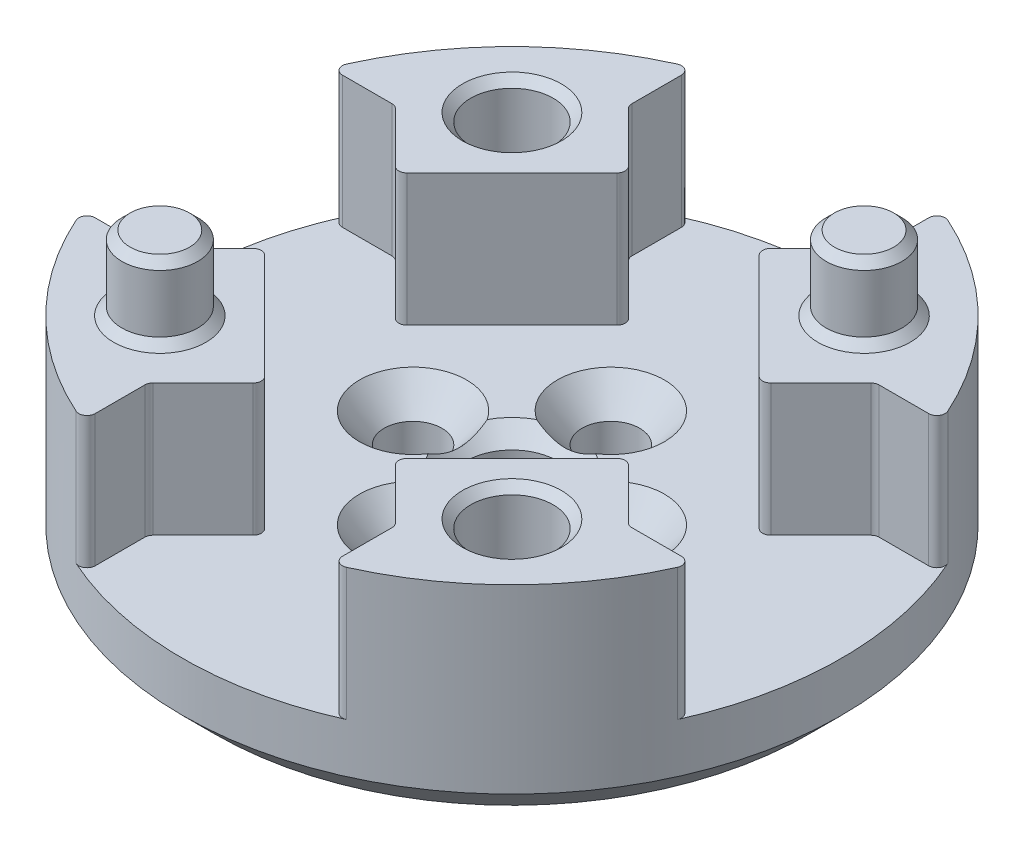
SolidWorks part; units mm, degrees
ref_plane "前视基准面" through (0, 0, 0) normal (0, 0, 1) x (1, 0, 0)
ref_plane "上视基准面" through (0, 0, 0) normal (0, 1, 0) x (1, 0, 0)
ref_plane "右视基准面" through (0, 0, 0) normal (1, 0, 0) x (0, 0, -1)
sketch "草图1" plane through (0, 0, 0) normal (0, 1, 0) x (1, 0, 0)
  circle A0 centre (0, 0) radius 20
  dimension "D1" = 40
extrude "凸台-拉伸1" add sketch "草图1" along normal blind 5
sketch "草图2" plane through (0, 5, 0) normal (0, 1, 0) x (1, 0, 0)
  line L0 (0, -15) -> (7.5, -7.5) construction
  line L1 (0, -15) -> (-7.5, -7.5) construction
  line L2 (7.5, -7.5) -> (0, 0) construction
  line L3 (-7.5, -7.5) -> (0, 0) construction
  line L4 (0, -15) -> (0, 0) construction
  line L5 (7.5, -7.5) -> (-7.5, -7.5) construction
  line L6 (14.5711, -7.5) -> (7.5, -14.5711) construction
  line L7 (14.5711, -7.5) -> (11.0355, -3.9645)
  line L8 (7.5, -14.5711) -> (3.9645, -11.0355)
  line L9 (11.0355, -3.9645) -> (3.9645, -11.0355)
  line L10 (14.5711, -7.5) -> (3.9645, -11.0355) construction
  line L11 (7.5, -14.5711) -> (11.0355, -3.9645) construction
  line L12 (7.5, -14.5711) -> (7.5, -18.5405)
  line L13 (14.5711, -7.5) -> (18.5405, -7.5)
  circle A0 centre (0, 0) radius 20 construction
  arc A1 (7.5, -18.5405) -> (18.5405, -7.5) centre (0, 0) ccw
  point P1 (0, -7.5)
  point P2 (9.2678, -9.2678)
  dimension "D1" = 15
  dimension "D2" = 5
  dimension "D3" = 5
extrude "凸台-拉伸2" add sketch "草图2" along normal blind 8
fillet "圆角1" radius 0.5 6 edges at (18.5405, 9, 7.5) (14.5711, 9, 7.5) (7.5, 9, 18.5405) (7.5, 9, 14.5711) (11.0355, 9, 3.9645) (3.9645, 9, 11.0355)
pattern_circular "阵列(圆周)1" count 4 over 360 about axis through (0, 5, 0) along (0, -1, 0) of "凸台-拉伸2", "圆角1" reverse direction yes
sketch "草图3" plane through (0, 13, 0) normal (0, 1, 0) x (1, 0, 0)
  line L0 (10.682, -10.682) -> (0, 0) construction
  line L1 (10.682, -4.318) -> (4.318, -10.682) construction
  line L2 (0, 0) -> (10.682, -10.682) construction
  circle A0 centre (10.682, -10.682) radius 2.5
  circle A1 centre (-10.682, -10.682) radius 2.5 construction
  circle A2 centre (-10.682, 10.682) radius 2.5
  circle A3 centre (10.682, 10.682) radius 2.5 construction
  circle A5 centre (10.682, 10.682) radius 2.3
  circle A6 centre (-10.682, -10.682) radius 2.3
  dimension "D2" = 5
  dimension "D1" = 4.5
  dimension "D3" = 4
  dimension "D4" = 15.1066
  dimension "D5" = 0.2
  dimension "D6" = 0.2
extrude "切除-拉伸1" cut sketch "草图3" against normal blind 5 contours A2 | A0 region at (10.682, 13, 10.682) region at (-10.682, 13, -10.682)
extrude "凸台-拉伸3" add sketch "草图3<3>" along normal blind 4.5 contours A3 | A1 | A5 | A6 region at (10.682, 13, -10.682) region at (-10.682, 13, 10.682)
sketch "草图3<3>" plane through (0, 13, 0) normal (0, 1, 0) x (1, 0, 0) same geometry as "草图3"
chamfer "倒角1" distance 0.5 angle 45 8 edges at (10.682, 13, 13.182) (10.682, 8, 13.182) (-10.682, 13, -8.182) (-10.682, 8, -8.182) (10.682, 13, -8.382) (10.682, 17.5, -8.382) (-10.682, 13, 12.982) (-10.682, 17.5, 12.982)
sketch "草图4" plane through (0, 0, 0) normal (0, -1, 0) x (1, 0, 0)
  circle A0 centre (0, 0) radius 2.75
  dimension "D1" = 5.5
extrude "切除-拉伸2" cut sketch "草图4" against normal through all
chamfer "倒角2" distance 2 angle 45 1 edges at (0, 0, 20)
sketch "草图5" plane through (0, 5, 0) normal (0, 1, 0) x (1, 0, 0)
  circle A0 centre (6, 0) radius 1.75
  point P2 (0, 0)
  dimension "D1" = 3.5
  dimension "D2" = 6
extrude "切除-拉伸3" cut sketch "草图5" against normal up to next
chamfer "倒角3" distance 1.5 angle 50 1 edges at (6, 5, 1.75) first distance on face at (6, 5, 1.75)
pattern_circular "阵列(圆周)2" count 4 over 360 about axis through (0, 5, 0) along (0, -1, 0) of "切除-拉伸3", "倒角3" reverse direction yes
chamfer "倒角4" distance 1 angle 45 4 edges at (1.9445, 5, -1.9445) (-1.9445, 5, -1.9445) (-1.9445, 5, 1.9445) (1.9445, 5, 1.9445)
